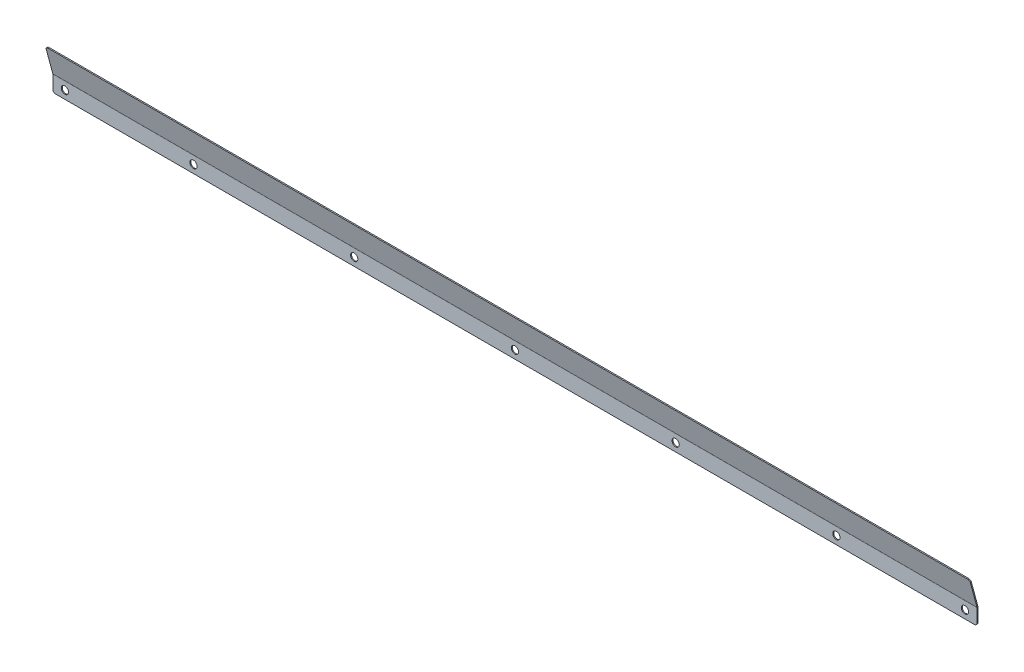
SolidWorks part; units mm, degrees
note: The reader was unsure of these and kept them because the rebuilt part matched: flange length of "Edge-Flange1".
other "Markup1"
sketch "Sketch11" plane through (-620, 119.8709, 0) normal (-0.3172, 0.1569, 0.9353) x (0.9484, 0.0512, 0.313)
material "AISI 304"
ref_plane "Front Plane" through (0, 0, 0) normal (0, 0, 1) x (1, 0, 0)
ref_plane "Top Plane" through (0, 0, 0) normal (0, 1, 0) x (1, 0, 0)
ref_plane "Right Plane" through (0, 0, 0) normal (1, 0, 0) x (0, 0, -1)
sketch "Sketch1" plane through (0, 0, 0) normal (0, 0, 1) x (1, 0, 0)
  line L0 (0, -5.6273) -> (0, 5.6273) construction
  line L1 (575, 10) -> (-575, 10)
  line L2 (575, 10) -> (575, -10)
  line L3 (575, -10) -> (-575, -10)
  line L4 (-575, 10) -> (-575, -10)
  line L5 (575, 10) -> (-575, -10) construction
  line L6 (575, -10) -> (-575, 10) construction
  point P0 (0, 0)
  point P5 (0, 0)
  dimension "D1" = 10
  dimension "D2" = 10
  dimension "D3" = 1150
base flange "Base-Flange1" sketch "Sketch1" thickness 1.2141 reverse thickness direction no parameters "D1"=1.27
edge flange "Edge-Flange1" sketch "Sketch13" flange angle 165 flange length 35 flange position material outside bend radius 1.27 thickness 1.2141 relief rectangular parameters "D6"=10
bend "EdgeBend2" bend radius 1.27 bend angle 15 parameters "D5"=1
sketch "Sketch13" plane through (0, 10, 0) normal (0, 0.2588, -0.9659) x (-1, 0, 0)
  line L0 (-575, 0) -> (575, 0) construction
  line L1 (-575, 0) -> (575, 0)
  line L2 (-575, 0) -> (-575, 34.8402)
  line L3 (-575, 34.8402) -> (575, 34.8402)
  line L4 (575, 34.8402) -> (575, 0)
hole_wizard "M8 Clearance Hole1" positions "Sketch9" profile "Sketch10" hole size "M8" standard "ANSI Metric" end condition up to next
sketch "Sketch9" plane through (0, 0, 0) normal (0, 0, 1) x (1, 0, 0)
  line L1 (5.6273, 0) -> (-5.6273, 0) construction
  line L3 (560, 0) -> (400, 0)
  line L4 (400, 0) -> (200, 0)
  line L5 (200, 0) -> (0, 0)
  line L6 (0, 0) -> (-200, 0)
  line L7 (-200, 0) -> (-400, 0)
  line L9 (-400, 0) -> (-560, 0)
  line L11 (575, -10) -> (575, 9.8328) construction
  point P2 (560, 0)
  point P34 (400, 0)
  point P37 (200, 0)
  point P40 (0, 0)
  point P43 (-200, 0)
  point P46 (-400, 0)
  point P49 (-560, 0)
  point P51 (557.661, 0)
  dimension "D1" = 200
  dimension "D2" = 15
sketch "Sketch10" plane through (560, 0, 0) normal (1, 0, 0) x (0, -1, 0)
  line L0 (0, 0) -> (0, 1.2141)
  line L1 (0, 1.2141) -> (4.5, 1.2141)
  line L2 (4.5, 1.2141) -> (4.5, 0)
  line L5 (4.5, 0) -> (0, 0)
  line L11 (0, -6.35) -> (0, 107.95) construction
  dimension "Thru Hole Dia." = 9
  dimension "Thru Hole Depth" = 1.2141
chamfer "Chamfer1" distance 2 4 edges at (-575, 43.8101, 8.4309) (-575, -10, -0.6071) (575, -10, -0.6071) (575, 43.8101, 8.4309)
sketch "Bend-Lines1" [suppressed] plane through (0, 0, 0) normal (0, 1, 0) x (1, 0, 0)
sketch "Bounding-Box1" [suppressed] plane through (0, 0, 0) normal (0, 1, 0) x (1, 0, 0)
sheet metal parameters "Sheet-Metal1" thickness 1.2141 parameters "D1"=2
flat pattern "Flat-Pattern1" [suppressed]
sketch "Bend-Lines2" plane through (0, 0, 0) normal (0, 1, 0) x (1, 0, 0)
sketch3d "Bounding-Box2" [suppressed]
  line L0 (609.6, -15, 0) -> (-609.6, -15, 0) construction
  line L1 (609.6, 30, 0) -> (-609.6, 30, 0) construction
  line L2 (609.6, -15, 0) -> (609.6, 30, 0) construction
  line L3 (-609.6, -15, 0) -> (-609.6, 30, 0) construction
sheet metal parameters "Sheet-Metal2" thickness 1.2141 parameters "D1"=2
flat pattern "Flat-Pattern1" [suppressed]
sketch "Bend-Lines2" plane through (0, 0, 0) normal (0, 0, 1) x (1, 0, 0)
  line L0 (609.6, 30.3497) -> (-609.6, 30.3497) construction
  line L1 (609.6, 30.3497) -> (-609.6, 30.3497) construction
sketch3d "Bounding-Box2" [suppressed]
  line L0 (-609.6, -15, 0) -> (609.6, -15, 0) construction
  line L1 (-609.6, 89.8709, 0) -> (609.6, 89.8709, 0) construction
  line L2 (-609.6, -15, 0) -> (-609.6, 89.8709, 0) construction
  line L3 (609.6, -15, 0) -> (609.6, 89.8709, 0) construction
bend of the flat pattern "Flatten-<EdgeBend2>1"
sheet metal parameters "Sheet-Metal3" thickness 1.2141 parameters "D1"=2
flat pattern "Flat-Pattern1"
sketch "Bend-Lines2" plane through (0, 0, 0) normal (0, 0, 1) x (1, 0, 0)
  line L2 (575, 10.0785) -> (-575, 10.0785) construction
  line L3 (575, 10.0785) -> (-575, 10.0785) construction
sketch3d "Bounding-Box2" [suppressed]
  line L0 (-575, -10, 0) -> (575, -10, 0) construction
  line L1 (-575, 44.9972, 0) -> (575, 44.9972, 0) construction
  line L2 (-575, -10, 0) -> (-575, 44.9972, 0) construction
  line L3 (575, -10, 0) -> (575, 44.9972, 0) construction
bend of the flat pattern "Flatten-<EdgeBend2>2"
